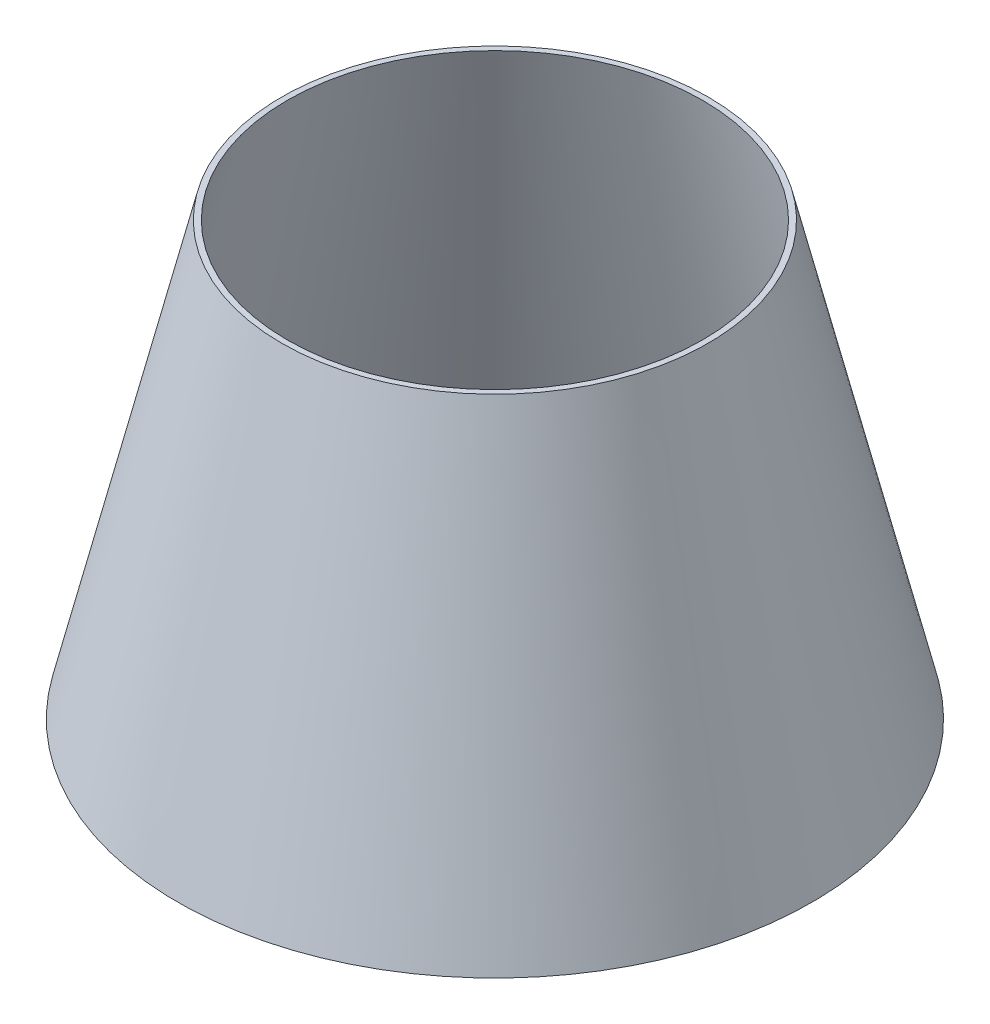
SolidWorks part; units mm, degrees
ref_plane "Front Plane" through (0, 0, 0) normal (0, 0, 1) x (1, 0, 0)
ref_plane "Top Plane" through (0, 0, 0) normal (0, 1, 0) x (1, 0, 0)
ref_plane "Right Plane" through (0, 0, 0) normal (1, 0, 0) x (0, 0, -1)
sketch "Sketch1" plane through (0, 0, 0) normal (0, 0, 1) x (1, 0, 0)
  line L0 (127, 271.5) -> (635, 271.5) construction
  line L1 (293.2418, 285.3139) -> (294.1823, 285.0662)
  line L3 (311.9493, 363.087) -> (293.2418, 285.3139)
  line L4 (349.8422, 375.0659) -> (349.8422, 279.4825) construction
  line L5 (349.8422, 375.0659) -> (349.8422, 279.4825) construction
  line L7 (311.9493, 363.087) -> (312.9525, 363.087)
  line L8 (312.9525, 363.087) -> (294.1823, 285.0662)
  dimension "D1" = 56.9
revolve "Revolve2" add sketch "Sketch1" angle 360 about L4
ref_plane "Plane1" through (0, 285.3139, 0) normal (0, -1, 0) x (-1, 0, 0)
sketch "Sketch3" plane through (0, 285.3139, 0) normal (0, -1, 0) x (-1, 0, 0)
  circle A0 centre (-349.8422, 0) radius 60.2209
extrude "Cut-Extrude2" cut sketch "Sketch3" against normal blind 1 and the other way blind 1
